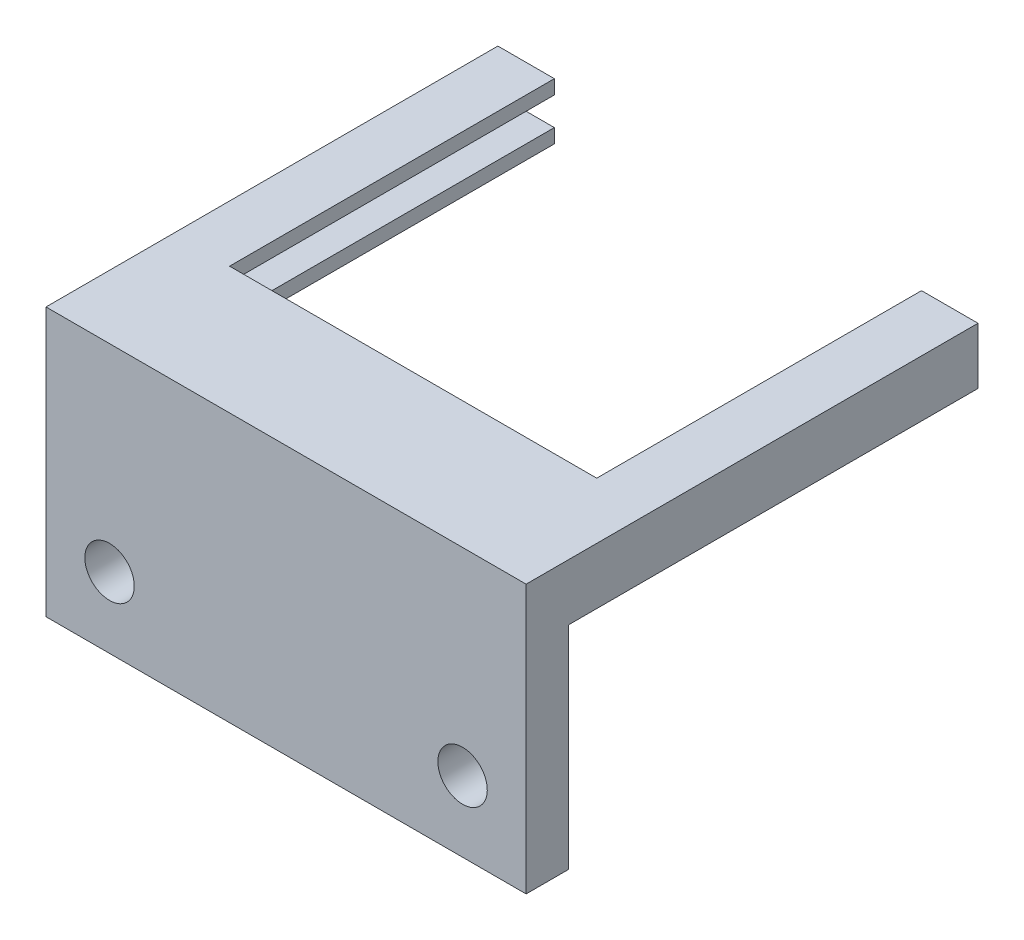
SolidWorks part; units mm, degrees
ref_plane "Front Plane" through (0, 0, 0) normal (0, 0, 1) x (1, 0, 0)
ref_plane "Top Plane" through (0, 0, 0) normal (0, 1, 0) x (1, 0, 0)
ref_plane "Right Plane" through (0, 0, 0) normal (1, 0, 0) x (0, 0, -1)
sketch "Sketch1" plane through (0, 0, 0) normal (0, 1, 0) x (1, 0, 0)
  line L1 (0, 0) -> (34, 0)
  line L2 (0, 0) -> (0, 29)
  line L3 (0, 29) -> (34, 29)
  line L4 (34, 0) -> (34, 29)
  dimension "D1" = 34
  dimension "D2" = 29
extrude "Boss-Extrude1" add sketch "Sketch1" along normal blind 4
sketch "Sketch2" plane through (0, 4, 0) normal (0, 1, 0) x (1, 0, 0)
  line L0 (34, 29) -> (0, 29) construction
  line L1 (0, 29) -> (4, 29) construction
  line L2 (4, 29) -> (30, 29)
  line L3 (4, 29) -> (4, 6)
  line L4 (4, 6) -> (30, 6)
  line L5 (30, 29) -> (30, 6)
  line L6 (30, 29) -> (34, 29) construction
  dimension "D1" = 26
  dimension "D2" = 23
extrude "Cut-Extrude1" cut sketch "Sketch2" against normal through all
sketch "Sketch3" plane through (0, 0, -29) normal (0, 0, -1) x (-1, 0, 0)
  line L0 (0, 4) -> (0, 0) construction
  line L1 (-1, 1) -> (-33, 1)
  line L2 (-1, 1) -> (-1, 3)
  line L3 (-1, 3) -> (-33, 3)
  line L4 (-33, 1) -> (-33, 3)
  line L5 (-4, 4) -> (0, 4) construction
  line L6 (-4, 0) -> (0, 0) construction
  line L7 (-34, 4) -> (-34, 0) construction
  point P6 (0, 2)
  dimension "D1" = 1
  dimension "D2" = 1
  dimension "D3" = 1
  dimension "D4" = 1
extrude "Cut-Extrude2" cut sketch "Sketch3" against normal blind 28
sketch "Sketch4" plane through (0, 0, 0) normal (-1, 0, 0) x (0, 0, 1)
  line L0 (0, 4) -> (3, 4)
  line L1 (3, 4) -> (3, -15)
  line L2 (3, -15) -> (0, -15)
  line L3 (0, -15) -> (0, 0)
  line L4 (-29, 4) -> (0, 4) construction
  line L5 (0, 0) -> (0, 4)
  dimension "D1" = 3
  dimension "D2" = 90
  dimension "D3" = 90
  dimension "D4" = 15
extrude "Boss-Extrude2" add sketch "Sketch4" against normal up to surface (34 mm away) up to face at (34, 2, -14.5)
sketch "Sketch5" plane through (0, 0, 0) normal (0, 0, -1) x (-1, 0, 0)
  line L0 (-29.5, -10) -> (-4.5, -10) construction
  line L1 (-34, -15) -> (0, -15) construction
  circle A0 centre (-29.5, -10) radius 1.75
  circle A1 centre (-4.5, -10) radius 1.75
  point P6 (-17, -15)
  point P7 (-17, -10)
  dimension "D1" = 3.5
  dimension "D2" = 25
  dimension "D3" = 5
extrude "Cut-Extrude3" cut sketch "Sketch5" against normal through all
equation "\"angle\" = 0"
equation "\"D2@Sketch4\"= 90 + \"angle\""
